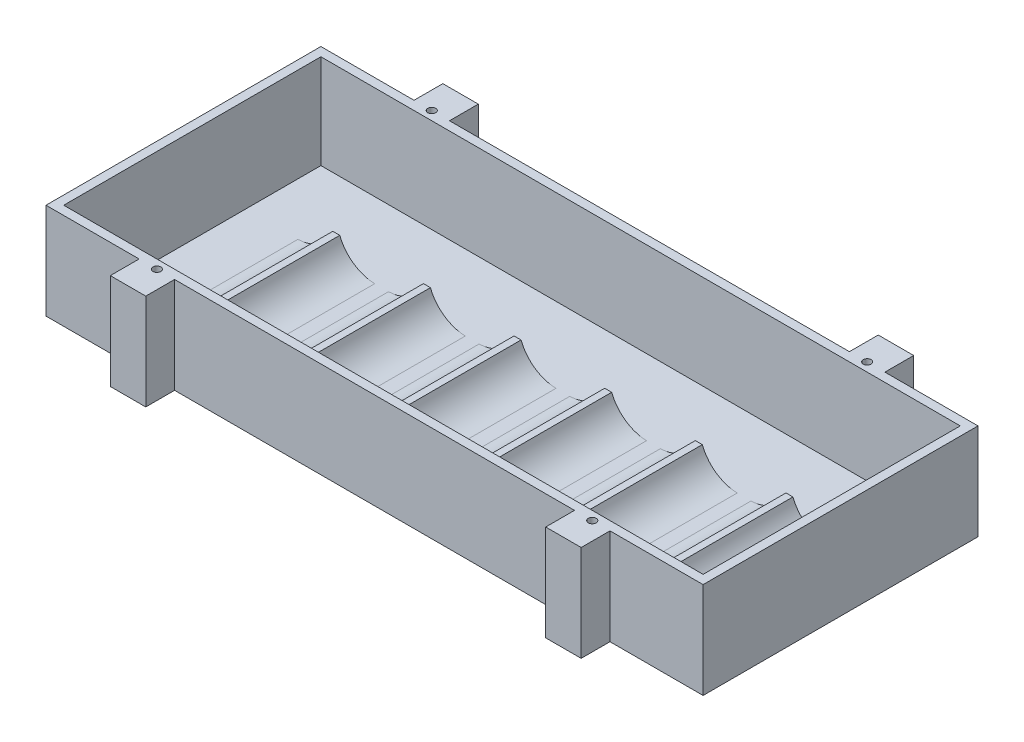
SolidWorks part; units mm, degrees
material "ABS"
ref_plane "Front Plane" through (0, 0, 0) normal (0, 0, 1) x (1, 0, 0)
ref_plane "Top Plane" through (0, 0, 0) normal (0, 1, 0) x (1, 0, 0)
ref_plane "Right Plane" through (0, 0, 0) normal (1, 0, 0) x (0, 0, -1)
sketch "Sketch1" plane through (0, 0, 0) normal (0, 1, 0) x (1, 0, 0)
  line L0 (2.54, -2.54) -> (2.54, -76.2)
  line L1 (0, 0) -> (188.214, 0)
  line L2 (0, 0) -> (0, -78.74)
  line L3 (0, -78.74) -> (188.214, -78.74)
  line L4 (188.214, 0) -> (188.214, -78.74)
  line L5 (2.54, -76.2) -> (185.674, -76.2)
  line L6 (185.674, -2.54) -> (185.674, -76.2)
  line L7 (2.54, -2.54) -> (185.674, -2.54)
  line L8 (0, 0) -> (0, 8.255)
  line L9 (0, 8.255) -> (188.214, 8.255)
  line L10 (188.214, 8.255) -> (188.214, 0)
  line L11 (0, -78.74) -> (0, -86.995)
  line L12 (0, -86.995) -> (188.214, -86.995)
  line L13 (188.214, -86.995) -> (188.214, -78.74)
  dimension "D1" = 73.66
  dimension "D2" = 183.134
  dimension "D4" = 10.795
  dimension "D5" = 95.25
  dimension "D3" = 2.54
extrude "Boss-Extrude1" add sketch "Sketch1" against normal blind 0.508 contours L2 L3 L4 L1
extrude "Boss-Extrude2" add sketch "Sketch1<3>" along normal blind 27 contours L10 L9 L8 L1 | L12 L13 L3 L11 | L4 L1 L2 L3 L0 L7 L6 L5 region at (94.107, 0, -4.1275) region at (94.107, 0, 2.0402) region at (94.107, 0, 82.8675)
sketch "Sketch1<3>" plane through (0, 0, 0) normal (0, 1, 0) x (1, 0, 0) same geometry as "Sketch1"
sketch "Sketch2" plane through (0, 0, 0) normal (0, 1, 0) x (-1, 0, 0)
  line L0 (-28.54, 0) -> (-28.54, 78.74) construction
  line L1 (-2.54, 2.54) -> (-2.54, 76.2) construction
  line L2 (-17.54, 0) -> (-17.54, 78.74) construction
  line L9 (0, 0) -> (-188.214, 0) construction
  line L10 (0, 78.74) -> (-188.214, 78.74) construction
  dimension "D1" = 26
  dimension "D2" = 15
sketch "Sketch5" plane through (0, 0, 2.54) normal (0, 0, 1) x (1, 0, 0)
  line L0 (28.54, 0) -> (28.54, 7) construction
  line L1 (29.54, 7) -> (27.54, 7)
  line L2 (0, 0) -> (188.214, 0) construction
  line L3 (17.54, 0) -> (39.54, 0)
  line L16 (55.4988, 7) -> (53.4988, 7)
  line L17 (43.4988, 0) -> (65.4988, 0)
  line L18 (54.4988, 0) -> (54.4988, 7) construction
  line L19 (81.4576, 7) -> (79.4576, 7)
  line L20 (69.4576, 0) -> (91.4576, 0)
  line L21 (80.4576, 0) -> (80.4576, 7) construction
  line L22 (107.4164, 7) -> (105.4164, 7)
  line L23 (95.4164, 0) -> (117.4164, 0)
  line L24 (106.4164, 0) -> (106.4164, 7) construction
  line L25 (133.3752, 7) -> (131.3752, 7)
  line L26 (121.3752, 0) -> (143.3752, 0)
  line L27 (132.3752, 0) -> (132.3752, 7) construction
  line L28 (159.334, 7) -> (157.334, 7)
  line L29 (147.334, 0) -> (169.334, 0)
  line L30 (158.334, 0) -> (158.334, 7) construction
  line L37 (170.06, 7) -> (168.06, 7) [skipped]
  line L38 (158.06, 0) -> (180.06, 0) [skipped]
  line L39 (169.06, 0) -> (169.06, 7) construction
  line L40 (145.64, 0) -> (145.64, 7) construction
  line L41 (134.64, 0) -> (156.64, 0) [skipped]
  line L42 (146.64, 7) -> (144.64, 7) [skipped]
  line L43 (122.22, 0) -> (122.22, 7) construction
  line L44 (111.22, 0) -> (133.22, 0) [skipped]
  line L45 (123.22, 7) -> (121.22, 7) [skipped]
  line L46 (98.8, 0) -> (98.8, 7) construction
  line L47 (87.8, 0) -> (109.8, 0) [skipped]
  line L48 (99.8, 7) -> (97.8, 7) [skipped]
  line L49 (75.38, 0) -> (75.38, 7) construction
  line L50 (64.38, 0) -> (86.38, 0) [skipped]
  line L51 (76.38, 7) -> (74.38, 7) [skipped]
  line L52 (51.96, 0) -> (51.96, 7) construction
  line L53 (40.96, 0) -> (62.96, 0) [skipped]
  line L54 (52.96, 7) -> (50.96, 7) [skipped]
  arc A0 (17.54, 0) -> (27.54, 7) centre (17.292, 10.9972) ccw
  arc A1 (39.54, 0) -> (29.54, 7) centre (39.788, 10.9972) cw
  arc A10 (65.4988, 0) -> (55.4988, 7) centre (65.7468, 10.9972) cw
  arc A11 (43.4988, 0) -> (53.4988, 7) centre (43.2508, 10.9972) ccw
  arc A12 (91.4576, 0) -> (81.4576, 7) centre (91.7056, 10.9972) cw
  arc A13 (69.4576, 0) -> (79.4576, 7) centre (69.2096, 10.9972) ccw
  arc A14 (117.4164, 0) -> (107.4164, 7) centre (117.6644, 10.9972) cw
  arc A15 (95.4164, 0) -> (105.4164, 7) centre (95.1684, 10.9972) ccw
  arc A16 (143.3752, 0) -> (133.3752, 7) centre (143.6232, 10.9972) cw
  arc A17 (121.3752, 0) -> (131.3752, 7) centre (121.1272, 10.9972) ccw
  arc A18 (169.334, 0) -> (159.334, 7) centre (169.582, 10.9972) cw
  arc A19 (147.334, 0) -> (157.334, 7) centre (147.086, 10.9972) ccw
  arc A24 (180.06, 0) -> (170.06, 7) centre (180.308, 10.9972) cw [skipped]
  arc A25 (158.06, 0) -> (168.06, 7) centre (157.812, 10.9972) ccw [skipped]
  arc A26 (134.64, 0) -> (144.64, 7) centre (134.392, 10.9972) ccw [skipped]
  arc A27 (156.64, 0) -> (146.64, 7) centre (156.888, 10.9972) cw [skipped]
  arc A28 (111.22, 0) -> (121.22, 7) centre (110.972, 10.9972) ccw [skipped]
  arc A29 (133.22, 0) -> (123.22, 7) centre (133.468, 10.9972) cw [skipped]
  arc A30 (87.8, 0) -> (97.8, 7) centre (87.552, 10.9972) ccw [skipped]
  arc A31 (109.8, 0) -> (99.8, 7) centre (110.048, 10.9972) cw [skipped]
  arc A32 (64.38, 0) -> (74.38, 7) centre (64.132, 10.9972) ccw [skipped]
  arc A33 (86.38, 0) -> (76.38, 7) centre (86.628, 10.9972) cw [skipped]
  arc A34 (62.96, 0) -> (52.96, 7) centre (63.208, 10.9972) cw [skipped]
  arc A35 (40.96, 0) -> (50.96, 7) centre (40.712, 10.9972) ccw [skipped]
  dimension "D2" = 11
  dimension "D1" = 1
  dimension "D3" = 7
  dimension "D6" = 25.9588
  dimension "D4" = 6
  dimension "D5" = 6
extrude "Boss-Extrude3" add sketch "Sketch5" along normal blind 32.5 from offset 21.59
extrude "Boss-Extrude4" add sketch "Sketch1<4>" against normal up to surface (0.508 mm away) contours L10 L9 L8 L1 | L12 L13 L3 L11 region at (94.107, 0, -4.1275) region at (94.107, 0, 82.8675) up to face at (94.107, -0.508, 39.37)
sketch "Sketch1<4>" plane through (0, 0, 0) normal (0, 1, 0) x (1, 0, 0) same geometry as "Sketch1"
sketch "Sketch6" plane through (0, 27, 0) normal (0, 1, 0) x (1, 0, 0)
  line L0 (0, 0) -> (188.214, 0) construction
  line L1 (188.214, 8.255) -> (188.214, -86.995) construction
  line L2 (0, -86.995) -> (0, 8.255) construction
  line L3 (0, -39.37) -> (14.6137, -39.37) construction
  point P5 (31.75, 0)
  point P6 (156.464, 0)
  point P9 (156.464, -78.74)
  point P10 (31.75, -78.74)
  dimension "D1" = 31.75
  dimension "D2" = 31.75
hole_wizard "#4-40 Tapped Hole2" positions "Sketch10" profile "Sketch9" tap size "#4-40" standard "Ansi Inch"
sketch "Sketch10" plane through (0, 27, 0) normal (0, 1, 0) x (-1, 0, 0)
  point P0 (-31.75, 0)
  point P1 (-156.464, 0)
  point P8 (-31.75, 78.74)
  point P11 (-156.464, 78.74)
sketch "Sketch9" plane through (31.75, 27, 0) normal (1, 0, 0) x (0, 0, 1)
  line L0 (0, 0) -> (0, 8.2992)
  line L1 (0, 8.2992) -> (1.1303, 7.62)
  line L2 (1.1303, 7.62) -> (1.1303, 0)
  line L5 (1.1303, 0) -> (0, 0)
  line L10 (0, 8.2992) -> (-1.1303, 7.62) construction
  line L11 (0, -6.35) -> (0, 107.95) construction
  dimension "Tap Drill Dia." = 2.2606
  dimension "Tap Drill Depth" = 7.62
  dimension "Drill Angle" = 118
cosmetic thread "Hole Thread2" parameters "D1"=5.588, "D2"=2.8448
cosmetic thread "Hole Thread3" parameters "D1"=5.588, "D2"=2.8448
cosmetic thread "Hole Thread4" parameters "D1"=5.588, "D2"=2.8448
cosmetic thread "Hole Thread5" parameters "D1"=5.588, "D2"=2.8448
sketch "midpoint" plane through (0, 27, 0) normal (0, 1, 0) x (1, 0, 0)
  line L0 (94.107, 8.255) -> (94.107, -86.995) construction
  line L1 (0, 8.255) -> (188.214, 8.255) construction
  line L2 (0, -86.995) -> (188.214, -86.995) construction
sketch "Sketch11" plane through (0, 27, 0) normal (0, 1, 0) x (1, 0, 0)
  line L0 (0, 8.255) -> (188.214, 8.255) construction
  line L1 (36.83, 8.255) -> (151.384, 8.255)
  line L2 (36.83, 8.255) -> (36.83, 0)
  line L3 (36.83, 0) -> (151.384, 0)
  line L4 (151.384, 8.255) -> (151.384, 0)
  line L5 (2.54, -2.54) -> (185.674, -2.54) construction
  line L6 (0, -39.37) -> (15.7032, -39.37) construction
  line L7 (0, -86.995) -> (0, 8.255) construction
  line L8 (151.384, -86.995) -> (151.384, -78.74)
  line L9 (36.83, -86.995) -> (151.384, -86.995)
  line L10 (36.83, -78.74) -> (151.384, -78.74)
  line L11 (36.83, -86.995) -> (36.83, -78.74)
  line L12 (94.107, 8.255) -> (94.107, -12.9141) construction
  line L13 (0, 8.255) -> (26.67, 8.255)
  line L14 (0, 8.255) -> (0, 0)
  line L15 (0, 0) -> (26.67, 0)
  line L16 (26.67, 8.255) -> (26.67, 0)
  line L17 (188.214, 8.255) -> (188.214, 0)
  line L18 (188.214, 8.255) -> (161.544, 8.255)
  line L19 (161.544, 8.255) -> (161.544, 0)
  line L20 (188.214, 0) -> (161.544, 0)
  line L21 (188.214, -86.995) -> (188.214, -78.74)
  line L22 (188.214, -86.995) -> (161.544, -86.995)
  line L23 (161.544, -86.995) -> (161.544, -78.74)
  line L24 (188.214, -78.74) -> (161.544, -78.74)
  line L25 (0, -86.995) -> (0, -78.74)
  line L26 (0, -86.995) -> (26.67, -86.995)
  line L27 (26.67, -86.995) -> (26.67, -78.74)
  line L28 (0, -78.74) -> (26.67, -78.74)
  dimension "D1" = 5.08
  dimension "D2" = 5.08
  dimension "D3" = 2.54
  dimension "D4" = 2.54
  dimension "D5" = 5.08
extrude "Cut-Extrude1" cut sketch "Sketch11" against normal through all
